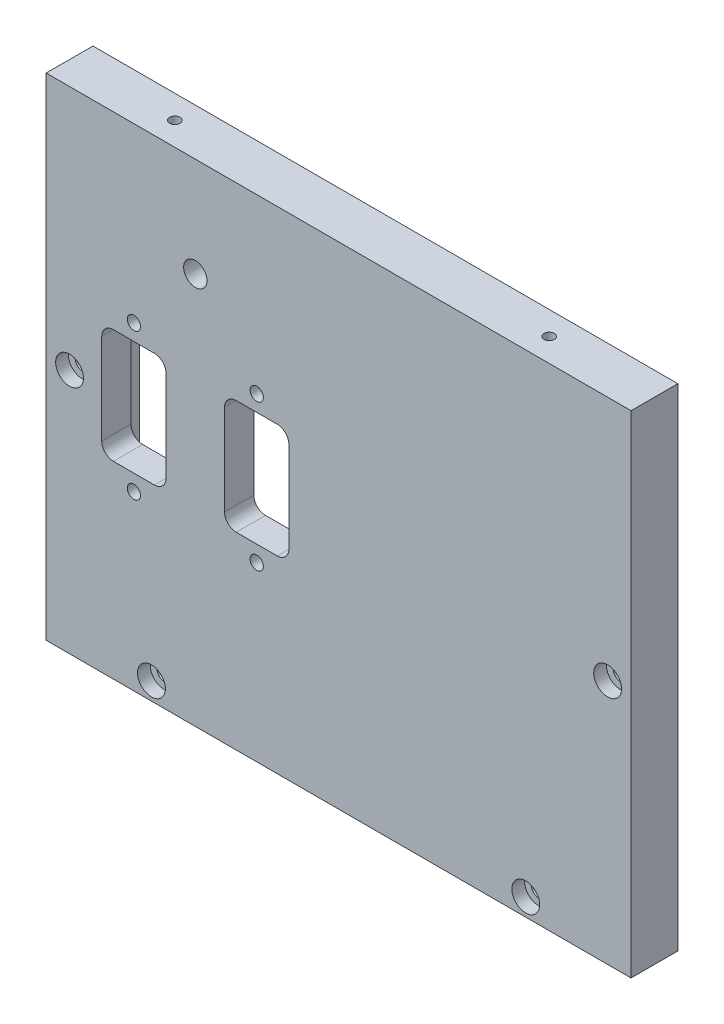
SolidWorks part; units mm, degrees
ref_plane "Front Plane" through (0, 0, 0) normal (0, 0, 1) x (1, 0, 0)
ref_plane "Top Plane" through (0, 0, 0) normal (0, 1, 0) x (1, 0, 0)
ref_plane "Right Plane" through (0, 0, 0) normal (1, 0, 0) x (0, 0, -1)
sketch "Sketch1" plane through (0, 0, 0) normal (0, 0, 1) x (1, 0, 0)
  line L1 (-50, 42) -> (50, 42)
  line L2 (-50, 42) -> (-50, -42)
  line L3 (-50, -42) -> (50, -42)
  line L4 (50, 42) -> (50, -42)
  line L5 (-50, 42) -> (50, -42) construction
  line L6 (-50, -42) -> (50, 42) construction
  point P0 (0, 0)
extrude "Boss-Extrude1" add sketch "Sketch1" along normal blind 8
sketch "Sketch2" plane through (0, 0, 8) normal (0, 0, 1) x (1, 0, 0)
  line L0 (-50, -42) -> (-50, -36) construction
  line L1 (-50, -36) -> (50, -36) construction
  line L2 (50, -42) -> (50, 42) construction
  line L3 (50, -36) -> (50, -42) construction
  line L4 (-50, -39) -> (-32, -39) construction
  line L5 (50, -39) -> (32, -39) construction
  point P12 (0, 0)
  point P13 (0, 0)
hole_wizard "CBORE for #2 Socket Head Cap Screw1" positions "3DSketch1" profile "Sketch3" counterbore size "#2" standard "ANSI Inch"
sketch3d "3DSketch1"
  point P0 (-32, -39, 8)
  point P3 (32, -39, 8)
sketch "Sketch3" plane through (-32, -39, 8) normal (1, 0, 0) x (0, -1, 0)
  line L0 (0, 0) -> (0, 13.0026)
  line L1 (0, 13.0026) -> (1.2192, 12.27)
  line L2 (1.2192, 12.27) -> (1.2192, 2.1844)
  line L3 (1.2192, 2.1844) -> (2.3812, 2.1844)
  line L4 (2.3812, 2.1844) -> (2.3812, 0)
  line L5 (2.3812, 0) -> (0, 0)
  line L10 (0, 13.0026) -> (-1.2192, 12.27) construction
  line L11 (0, -6.35) -> (0, 107.95) construction
  dimension "Hole Dia." = 2.4384
  dimension "Hole Depth" = 12.27
  dimension "C'Bore Dia." = 4.7625
  dimension "C'Bore Depth" = 2.1844
  dimension "Drill Angle" = 118
sketch "Sketch4" plane through (0, 0, 8) normal (0, 0, 1) x (1, 0, 0)
  line L0 (-50, -42) -> (-42, -42) construction
  line L1 (-42, -42) -> (-42, 42) construction
  line L2 (50, 42) -> (-50, 42) construction
  line L3 (-42, 42) -> (-50, 42) construction
  line L4 (50, -42) -> (42, -42) construction
  line L5 (42, -42) -> (42, 42) construction
  line L6 (42, 42) -> (50, 42) construction
  line L7 (46, -42) -> (46, 0) construction
  line L8 (-46, -42) -> (-46, 0) construction
hole_wizard "CBORE for #2 Socket Head Cap Screw2" positions "3DSketch2" profile "Sketch5" counterbore size "#2" standard "ANSI Inch"
sketch3d "3DSketch2"
  point P0 (-46, 0, 8)
  point P3 (46, 0, 8)
sketch "Sketch5" plane through (-46, 0, 8) normal (1, 0, 0) x (0, -1, 0)
  line L0 (0, 0) -> (0, 13.0026)
  line L1 (0, 13.0026) -> (1.2192, 12.27)
  line L2 (1.2192, 12.27) -> (1.2192, 2.1844)
  line L3 (1.2192, 2.1844) -> (2.3812, 2.1844)
  line L4 (2.3812, 2.1844) -> (2.3812, 0)
  line L5 (2.3812, 0) -> (0, 0)
  line L10 (0, 13.0026) -> (-1.2192, 12.27) construction
  line L11 (0, -6.35) -> (0, 107.95) construction
  dimension "Hole Dia." = 2.4384
  dimension "Hole Depth" = 12.27
  dimension "C'Bore Dia." = 4.7625
  dimension "C'Bore Depth" = 2.1844
  dimension "Drill Angle" = 118
sketch "Sketch6" plane through (0, 42, 0) normal (0, 1, 0) x (1, 0, 0)
  line L0 (-50, -4) -> (-32, -4) construction
  line L1 (-50, -8) -> (-50, 0) construction
  line L2 (50, -4) -> (32, -4) construction
  line L3 (50, -8) -> (50, 0) construction
hole_wizard "#2-56 Tapped Hole1" positions "3DSketch3" profile "Sketch7" tap size "#2-56" standard "ANSI Inch"
sketch3d "3DSketch3"
  point P0 (-32, 42, 4)
  point P3 (32, 42, 4)
sketch "Sketch7" plane through (-32, 42, 4) normal (1, 0, 0) x (0, 0, 1)
  line L0 (0, 0) -> (0, 12.5342)
  line L1 (0, 12.5342) -> (0.889, 12)
  line L2 (0.889, 12) -> (0.889, 0)
  line L5 (0.889, 0) -> (0, 0)
  line L10 (0, 12.5342) -> (-0.889, 12) construction
  line L11 (0, -6.35) -> (0, 107.95) construction
  dimension "Tap Drill Dia." = 1.778
  dimension "Tap Drill Depth" = 12
  dimension "Drill Angle" = 118
cosmetic thread "Hole Thread1" parameters "D1"=10, "D2"=2.1844
cosmetic thread "Hole Thread2" parameters "D1"=10, "D2"=2.1844
sketch "Sketch8" plane through (0, 0, 0) normal (0, 0, -1) x (-1, 0, 0)
  line L0 (-50, -42) -> (-50, -30) construction
  line L1 (-50, -30) -> (50, -30) construction
  line L2 (50, 42) -> (50, -42) construction
  line L3 (50, -30) -> (50, -42) construction
sketch "Sketch9" plane through (0, 0, 0) normal (0, 0, -1) x (-1, 0, 0)
  line L0 (50, -42) -> (42, -42) construction
  line L1 (42, -42) -> (42, 42) construction
  line L2 (-50, 42) -> (50, 42) construction
  line L3 (-50, -42) -> (-42, -42) construction
  line L4 (-42, -42) -> (-42, 42) construction
  line L5 (-50, 42) -> (-32, 42) construction
sketch "Sketch10" plane through (0, 0, 0) normal (0, 0, -1) x (-1, 0, 0)
  line L0 (-42, -42) -> (-37, -42) construction
  line L1 (-37, -42) -> (-37, 42) construction
  line L2 (-50, 42) -> (50, 42) construction
  line L3 (-37, -42) -> (-27, -42) construction
  line L4 (-27, -42) -> (-27, 42) construction
  line L5 (-27, -42) -> (3, -42) construction
  line L6 (3, -42) -> (3, 42) construction
  line L7 (3, -42) -> (7, -42) construction
  line L8 (7, -42) -> (7, 42) construction
sketch "Sketch12" plane through (0, 0, 0) normal (0, 0, -1) x (-1, 0, 0)
  line L0 (7, -42) -> (7, -30) construction
  line L1 (-50, -30) -> (50, -30) construction
  line L2 (7, -30) -> (42, -30) construction
  line L3 (42, -42) -> (42, 42) construction
  line L4 (42, -30) -> (42, 30) construction
  line L5 (42, 30) -> (7, 30) construction
  line L6 (7, -42) -> (7, 42) construction
  line L7 (7, 30) -> (7, -30) construction
  line L9 (7, 30) -> (42, 30)
  line L10 (7, 30) -> (7, -30)
  line L11 (7, -30) -> (42, -30)
  line L12 (42, 30) -> (42, -30)
extrude "Cut-Extrude3" cut sketch "Sketch12" against normal blind 3
fillet "Fillet1" radius 2 1 edges at (-7, 30, 1.5)
fillet "Fillet2" radius 2 1 edges at (-42, 30, 1.5)
fillet "Fillet3" radius 2 1 edges at (-42, -30, 1.5)
fillet "Fillet4" radius 2 1 edges at (-7, -30, 1.5)
sketch "Sketch13" plane through (0, 0, 3) normal (0, 0, -1) x (-1, 0, 0)
  line L0 (40, -30) -> (9, -30) construction
  line L1 (9, -30) -> (24.5, 0) construction
  line L2 (24.5, 0) -> (40, -30) construction
  line L3 (24.5, 0) -> (42, 0) construction
  line L4 (42, -28) -> (42, 28) construction
sketch "Sketch14" plane through (0, 0, 3) normal (0, 0, -1) x (-1, 0, 0)
  line L0 (24.5, 0) -> (7, 0) construction
  line L1 (7, 28) -> (7, -28) construction
sketch "Sketch15" plane through (0, 0, 3) normal (0, 0, -1) x (-1, 0, 0)
  line L0 (24.5, 0) -> (29.5, 0) construction
  line L1 (24.5, 0) -> (19.5, 0) construction
  line L2 (29.5, 0) -> (40.5, 0) construction
  line L3 (40.5, 0) -> (40.5, 9.75) construction
sketch "Sketch16" plane through (0, 0, 3) normal (0, 0, -1) x (-1, 0, 0)
  line L0 (19.5, 0) -> (8.5, 0) construction
  line L1 (19.5, 0) -> (19.5, -9.75) construction
  line L2 (8.5, 0) -> (8.5, 9.75) construction
  line L3 (29.5, 0) -> (29.5, -9.75) construction
  line L4 (8.5, 9.75) -> (19.5, 9.75)
  line L5 (8.5, 9.75) -> (8.5, -9.75)
  line L6 (8.5, -9.75) -> (19.5, -9.75)
  line L7 (19.5, 9.75) -> (19.5, -9.75)
sketch "Sketch17" plane through (0, 0, 3) normal (0, 0, -1) x (-1, 0, 0)
  line L1 (29.5, -9.75) -> (40.5, -9.75)
  line L2 (29.5, -9.75) -> (29.5, 9.75)
  line L3 (29.5, 9.75) -> (40.5, 9.75)
  line L4 (40.5, -9.75) -> (40.5, 9.75)
extrude "Cut-Extrude4" cut sketch "Sketch17" against normal blind 8 contours L2 L1 L4 L3
extrude "Cut-Extrude5" cut sketch "Sketch16" against normal blind 8
fillet "Fillet5" radius 2 2 edges at (-40.5, 9.75, 5.5) (-19.5, 9.75, 5.5)
fillet "Fillet6" radius 2 2 edges at (-29.5, 9.75, 5.5) (-8.5, 9.75, 5.5)
fillet "Fillet7" radius 2 2 edges at (-29.5, -9.75, 5.5) (-8.5, -9.75, 5.5)
fillet "Fillet8" radius 2 2 edges at (-40.5, -9.75, 5.5) (-19.5, -9.75, 5.5)
sketch "Sketch19" plane through (0, 0, 8) normal (0, 0, 1) x (1, 0, 0)
  line L0 (-38.5, 9.75) -> (-31.5, 9.75) construction
  line L1 (-38.5, 9.75) -> (-31.5, 9.75) construction
  line L4 (-38.5, 12.5) -> (-38.5, 9.75) construction
  line L5 (-38.5, 12.5) -> (-35, 12.5) construction
  line L6 (-35, 12.5) -> (-35, 9.75) construction
  line L7 (-17.5, 9.75) -> (-10.5, 9.75) construction
  line L8 (-10.5, 9.75) -> (-10.5, 12.5) construction
  line L9 (-10.5, 12.5) -> (-14, 12.5) construction
  line L10 (-14, 12.5) -> (-14, 9.75) construction
  line L11 (-10.5, -9.75) -> (-17.5, -9.75) construction
  line L15 (-10.5, -9.75) -> (-14, -9.75) construction
  line L16 (-14, -9.75) -> (-14, -12.5) construction
  line L17 (-38.5, -9.75) -> (-31.5, -9.75) construction
  line L18 (-31.5, -9.75) -> (-31.5, -12.5) construction
  line L19 (-31.5, -12.5) -> (-35, -12.5) construction
  line L20 (-35, -12.5) -> (-35, -9.75) construction
  arc A0 (-29.5, 7.75) -> (-31.5, 9.75) centre (-31.5, 7.75) ccw construction
hole_wizard "#4-40 Tapped Hole1" positions "3DSketch4" profile "Sketch20" tap size "#4-40" standard "ANSI Inch" end condition through all
sketch3d "3DSketch4"
  point P0 (-35, 12.5, 8)
  point P3 (-35, -12.5, 8)
  point P6 (-14, -12.5, 8)
  point P9 (-14, 12.5, 8)
sketch "Sketch20" plane through (-35, 12.5, 8) normal (1, 0, 0) x (0, -1, 0)
  line L0 (0, 0) -> (0, 8)
  line L1 (0, 8) -> (1.1303, 8)
  line L2 (1.1303, 8) -> (1.1303, 0)
  line L5 (1.1303, 0) -> (0, 0)
  line L11 (0, -6.35) -> (0, 107.95) construction
  dimension "Thru Tap Drill Dia." = 2.2606
  dimension "Thru Tap Drill Depth" = 8
cosmetic thread "Hole Thread3" parameters "D2"=2.8448
cosmetic thread "Hole Thread4" parameters "D2"=2.8448
cosmetic thread "Hole Thread5" parameters "D2"=2.8448
cosmetic thread "Hole Thread6" parameters "D2"=2.8448
sketch "Sketch21" plane through (0, 0, 3) normal (0, 0, -1) x (-1, 0, 0)
  line L0 (24.5, 0) -> (24.5, 25) construction
  circle A0 centre (24.5, 25) radius 2
extrude "Cut-Extrude6" cut sketch "Sketch21" against normal blind 8
